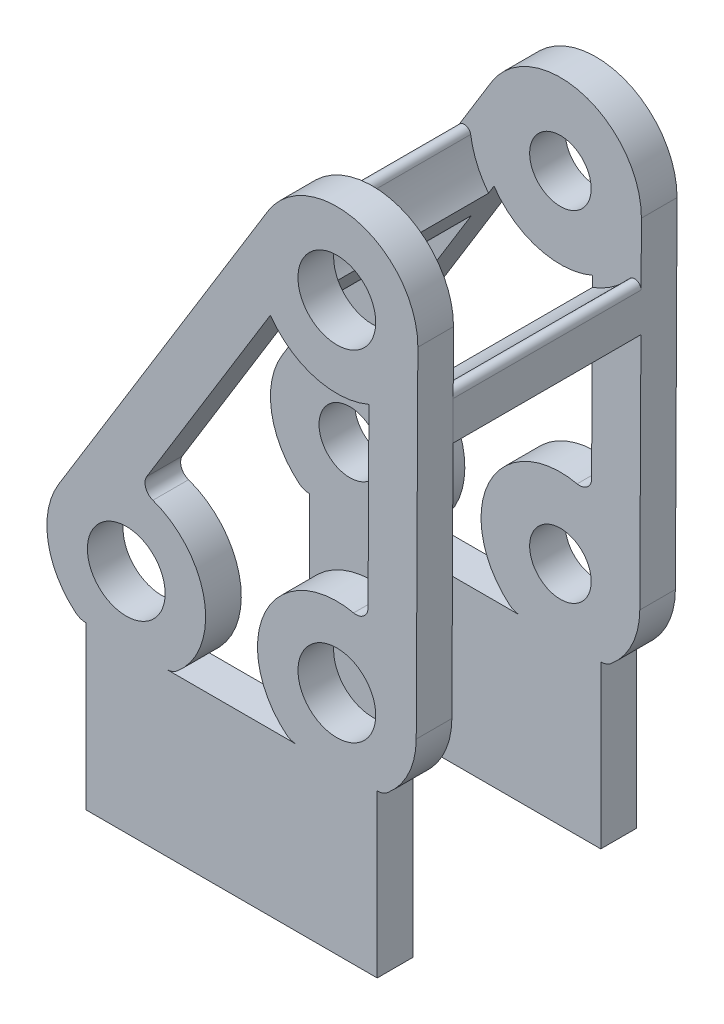
SolidWorks part; units mm, degrees
ref_plane "Front Plane" through (0, 0, 0) normal (0, 0, 1) x (1, 0, 0)
ref_plane "Top Plane" through (0, 0, 0) normal (0, 1, 0) x (1, 0, 0)
ref_plane "Right Plane" through (0, 0, 0) normal (1, 0, 0) x (0, 0, -1)
sketch "housing" plane through (0, 0, 0) normal (0, 0, 1) x (1, 0, 0)
  line L2 (-1.246, -2) -> (1.246, -2)
  line L3 (5.254, -2) -> (7.746, -2)
  line L4 (-2.0884, 1.2811) -> (4.369, 11.8073)
  line L5 (8.95, -0.0117) -> (9, 10.4881)
  line L6 (0.6321, 2.8471) -> (4.4495, 9.0698)
  line L9 (7.4631, 2.7528) -> (7.4891, 8.204)
  arc A1 (4.4495, 9.0698) -> (7.4891, 8.204) centre (6.5, 10.5) ccw
  arc A2 (9, 10.4881) -> (4.369, 11.8073) centre (6.5, 10.5) ccw
  circle A3 centre (0, 0) radius 0.95
  circle A4 centre (6.5, 0) radius 0.95
  arc A5 (1.5655, -1.8846) -> (0.8223, 2.3079) centre (0, 0) ccw
  arc A6 (-2.0884, 1.2811) -> (-1.5655, -1.8846) centre (0, 0) ccw
  arc A7 (8.0655, -1.8846) -> (8.95, -0.0117) centre (6.5, 0) ccw
  arc A8 (7.0173, 2.3948) -> (4.9345, -1.8846) centre (6.5, 0) ccw
  arc A9 (-1.5655, -1.8846) -> (-1.246, -2) centre (-1.246, -1.5) ccw
  arc A10 (4.9345, -1.8846) -> (5.254, -2) centre (5.254, -1.5) ccw
  arc A11 (7.746, -2) -> (8.0655, -1.8846) centre (7.746, -1.5) ccw
  arc A12 (1.246, -2) -> (1.5655, -1.8846) centre (1.246, -1.5) ccw
  circle A13 centre (6.5, 10.5) radius 0.95
  arc A19 (0.6321, 2.8471) -> (0.8223, 2.3079) centre (0.9459, 2.6546) ccw
  arc A20 (7.0173, 2.3948) -> (7.4631, 2.7528) centre (7.095, 2.7546) ccw
  dimension "D1" = 1.9
  dimension "D4" = 2.5
  dimension "D5" = 6.5
  dimension "D7" = 0.3681
  dimension "D8" = 0.5
  dimension "D2" = 10.5
  dimension "D3" = 1.5
  dimension "D6" = 2
extrude "Boss-Extrude1" add sketch "housing" along normal blind 8 contours A20 A8 A10 L3 A11 A7 L5 A2 L4 A6 A9 L2 A12 A5 A19 L6 A1 L9 A13 A4 A3 region at (-1.3517, -1.7928, 0)
ref_plane "Plane1" through (0, 0, 4) normal (0, 0, 1) x (1, 0, 0)
sketch "Sketch2" plane through (0, 0, 4) normal (0, 0, 1) x (1, 0, 0)
  line L1 (9.3, 13) -> (-2.7, 13)
  line L2 (9.3, 13) -> (9.3, -3)
  line L3 (9.3, -3) -> (-2.7, -3)
  line L4 (-2.7, 13) -> (-2.7, -3)
  dimension "D1" = 12
  dimension "D2" = 16
  dimension "D3" = 3
  dimension "D4" = 2.7
extrude "Cut-Extrude1" cut sketch "Sketch2" against normal mid plane 5.8
sketch "Sketch3" plane through (0, 0, 1.1) normal (0, 0, 1) x (1, 0, 0)
  line L0 (8.95, -0.0117) -> (9, 10.4881) construction
  line L1 (7.4631, 2.7528) -> (7.4891, 8.204) construction
  line L2 (0.6321, 2.8471) -> (4.4495, 9.0698) construction
  line L3 (-2.0884, 1.2811) -> (4.369, 11.8073) construction
  line L4 (8.9851, 7.3656) -> (8.994, 9.2272)
  line L5 (7.4815, 6.6223) -> (7.4875, 7.8799)
  line L6 (3.6224, 7.7216) -> (4.28, 8.7936)
  line L7 (2.7362, 9.1457) -> (3.7097, 10.7324)
  arc A0 (3.7097, 10.7324) -> (4.28, 8.7936) centre (6.5, 10.5) ccw
  arc A2 (2.7362, 9.1457) -> (3.6224, 7.7216) centre (6.5, 10.5) ccw
  arc A3 (7.4815, 6.6223) -> (8.9851, 7.3656) centre (6.5, 10.5) ccw
  arc A5 (7.4875, 7.8799) -> (8.994, 9.2272) centre (6.5, 10.5) ccw
  dimension "D1" = 2.8
  dimension "D2" = 8
extrude "Boss-Extrude2" add sketch "Sketch3" along normal up to surface (5.8 mm away) up to face at (5.55, 0, 6.9)
fillet "Fillet1" radius 0.2 3 edges at (8.994, 9.2272, 4) (3.7097, 10.7324, 4) (3.6224, 7.7216, 4)
sketch "Sketch4" plane through (0, 0, 8) normal (0, 0, 1) x (1, 0, 0)
  circle A0 centre (6.5, 10.5) radius 1.2
  circle A1 centre (0, 0) radius 1.2
  circle A2 centre (6.5, 0) radius 1.2
  dimension "D1" = 2.4
extrude "Cut-Extrude2" cut sketch "Sketch4" against normal up to surface (1.1 mm away) up to face at (5.55, 10.5, 6.9)
sketch "Sketch5" plane through (0, -2, 0) normal (0, -1, 0) x (1, 0, 0)
  line L1 (-1.246, 8) -> (7.746, 8)
  line L2 (-1.246, 8) -> (-1.246, 6.9)
  line L3 (-1.246, 6.9) -> (7.746, 6.9)
  line L4 (7.746, 8) -> (7.746, 6.9)
  line L5 (-1.246, 1.1) -> (7.746, 1.1)
  line L6 (-1.246, 1.1) -> (-1.246, 0)
  line L7 (-1.246, 0) -> (7.746, 0)
  line L8 (7.746, 1.1) -> (7.746, 0)
extrude "Boss-Extrude3" add sketch "Sketch5" along normal blind 5
split "Split1" bodies to split 109 resulting bodies 106 107 split by face at (5.3, 10.5, 6.9)
